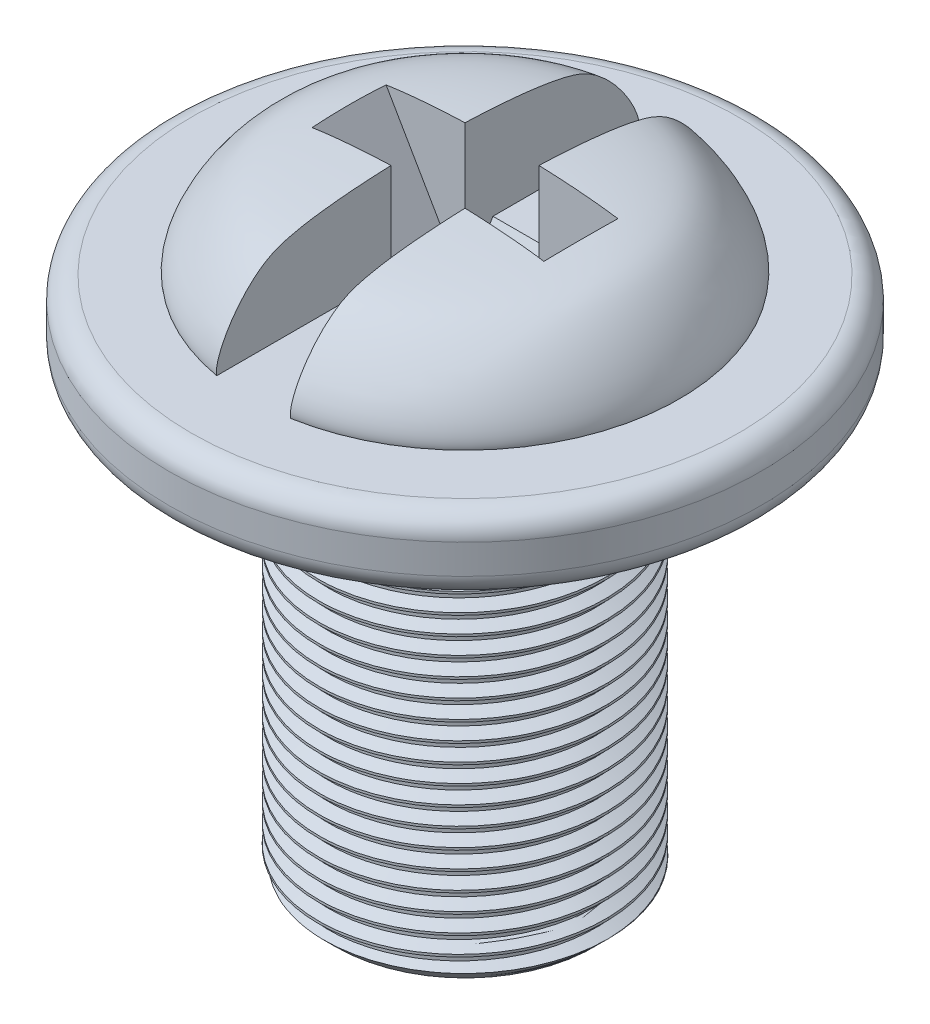
SolidWorks part; units mm, degrees
material "1023 Carbon Steel Sheet (SS)"
ref_plane "Front Plane" through (0, 0, 0) normal (0, 0, 1) x (1, 0, 0)
ref_plane "Top Plane" through (0, 0, 0) normal (0, 1, 0) x (1, 0, 0)
ref_plane "Right Plane" through (0, 0, 0) normal (1, 0, 0) x (0, 0, -1)
sketch "Sketch1" plane through (0, 0, 0) normal (0, 1, 0) x (1, 0, 0)
  circle A0 centre (0, 0) radius 4
  dimension "D1" = 8
extrude "Boss-Extrude1" add sketch "Sketch1" along normal blind 1
sketch "Sketch2" plane through (0, 0, 0) normal (0, -1, 0) x (1, 0, 0)
  circle A0 centre (0, 0) radius 1.939
  dimension "D1" = 3.878
extrude "Boss-Extrude2" add sketch "Sketch2" along normal blind 6
chamfer "Chamfer1" distance 0.2 angle 45 1 edges at (0, -6, -1.939)
thread "Thread1" pitch 0.25 method cut profile "Thread Profile1" start angle 0, offset 1, length 6, pitch 0.25, diameter 3.878
ref_plane "Plane1" through (1.939, -6.8, 0) normal (0, 0, 1) x (1, 0, 0)
sketch "Thread Profile1" plane through (1.939, -6.8, 0) normal (0, 0, 1) x (1, 0, 0)
  line L0 (0, 0) -> (0, 0.25) construction
  line L11 (0, 0) -> (0, 0.2187)
  line L12 (0, 0.2187) -> (-0.1353, 0.1406)
  line L13 (-0.1353, 0.1406) -> (-0.1353, 0.0781)
  line L15 (-0.1353, 0.0781) -> (0, 0)
  line L17 (-0.1353, 0.1094) -> (0, 0.1094) construction
  point P2 (0, 0)
  dimension "Pitch" = 0.25
  dimension "Profile_Angle" = 60
  dimension "Profile_Land" = 0.0625
  dimension "Profile_Height" = 0.1353
fillet "Fillet1" radius 0.3 2 edges at (0, 1, 4) (0, 0, 4)
sketch "Sketch3" plane through (0, 0, 0) normal (0, 0, 1) x (1, 0, 0)
  line L0 (-3.7, 1) -> (-2.9, 1) construction
  line L1 (3.7, 1) -> (-3.7, 1) construction
  line L2 (0, 1) -> (-2.9, 1)
  line L3 (0, 1) -> (0, 2.3)
  spline S0 degree 3 poles (-2.9, 1) (-2.9424, 1.1883) (-2.631, 1.7868) (-1.7724, 2.2944) (-0.0309, 2.3081) (0, 2.3) knots 0 0 0 0 0.443998 0.543998 1 1 1 1
  dimension "D1" = 0.8
  dimension "D2" = 1.3
revolve "Revolve1" add sketch "Sketch3" angle 360 about L3
sketch "Sketch4" plane through (0, 1, 0) normal (0, 1, 0) x (1, 0, 0)
  line L1 (-0.5, 3) -> (0.5, 3)
  line L2 (-0.5, 3) -> (-0.5, -3)
  line L3 (-0.5, -3) -> (0.5, -3)
  line L4 (0.5, 3) -> (0.5, -3)
  dimension "D1" = 1
  dimension "D2" = 0.5
  dimension "D3" = 6
  dimension "D4" = 3
extrude "Cut-Extrude1" cut sketch "Sketch4" along normal blind 10
sketch "Sketch6" plane through (0, 0, 0) normal (1, 0, 0) x (0, 0, -1)
  line L0 (0, 0) -> (-0.3, 0)
  line L1 (-1.939, 0) -> (1.939, 0) construction
  line L2 (-0.3, 0) -> (-1.5668, 2.1942)
  line L3 (-1.5668, 2.1942) -> (1.5668, 2.1942)
  line L4 (1.5668, 2.1942) -> (0.3, 0)
  line L5 (0.3, 0) -> (0, 0)
  line L6 (-0.8774, 1) -> (0.8774, 1) construction
  line L7 (2.8566, 1) -> (-2.8566, 1) construction
  spline S0 degree 3 poles (-2.8566, 1) (-2.8649, 1.0365) (-2.8615, 1.0739) (-2.8488, 1.1464) (-2.8387, 1.1815) (-2.8027, 1.2853) (-2.7708, 1.3521) (-2.6644, 1.5431) (-2.5772, 1.662) (-2.4276, 1.822) (-2.3747, 1.872) (-2.2614, 1.9638) (-2.2001, 2.0061) (-2.0065, 2.1057) (-1.8644, 2.1398) (-1.4362, 2.2221) (-1.1483, 2.247) (-0.5716, 2.2839) (-0.2825, 2.2928) (0.297, 2.2925) (0.5865, 2.2833) (1.1648, 2.2456) (1.454, 2.2201) (1.8804, 2.1359) (2.0212, 2.1009) (2.2789, 1.9624) (2.3866, 1.8672) (2.5833, 1.654) (2.6681, 1.5373) (2.7723, 1.349) (2.8035, 1.2835) (2.8392, 1.1799) (2.8491, 1.1448) (2.8616, 1.0727) (2.8649, 1.0362) (2.8566, 1) knots 0 0 0 0 0.015625 0.015625 0.03125 0.03125 0.0625 0.0625 0.125 0.125 0.15625 0.15625 0.1875 0.1875 0.25 0.25 0.375 0.375 0.5 0.5 0.625 0.625 0.75 0.75 0.8125 0.8125 0.875 0.875 0.9375 0.9375 0.96875 0.96875 0.984375 0.984375 1 1 1 1 construction
  dimension "D1" = 0.3
  dimension "D2" = 0.3
  dimension "D3" = 120
  dimension "D4" = 120
extrude "Cut-Extrude3" cut sketch "Sketch6" against normal blind 0.5 and the other way blind 0.5
sketch "Sketch7" plane through (0, 0, 0) normal (0, 0, 1) x (1, 0, 0)
  line L0 (0, 0) -> (-0.3, 0)
  line L1 (-1.939, 0) -> (1.939, 0) construction
  line L2 (-0.3, 0) -> (-2.1508, 3.2057)
  line L3 (-2.1508, 3.2057) -> (2.1508, 3.2057)
  line L4 (2.1508, 3.2057) -> (0.3, 0)
  line L5 (0.3, 0) -> (0, 0)
  dimension "D1" = 0.3
  dimension "D2" = 0.3
  dimension "D3" = 120
  dimension "D4" = 120
extrude "Cut-Extrude4" cut sketch "Sketch7" against normal blind 0.5 and the other way blind 0.5
